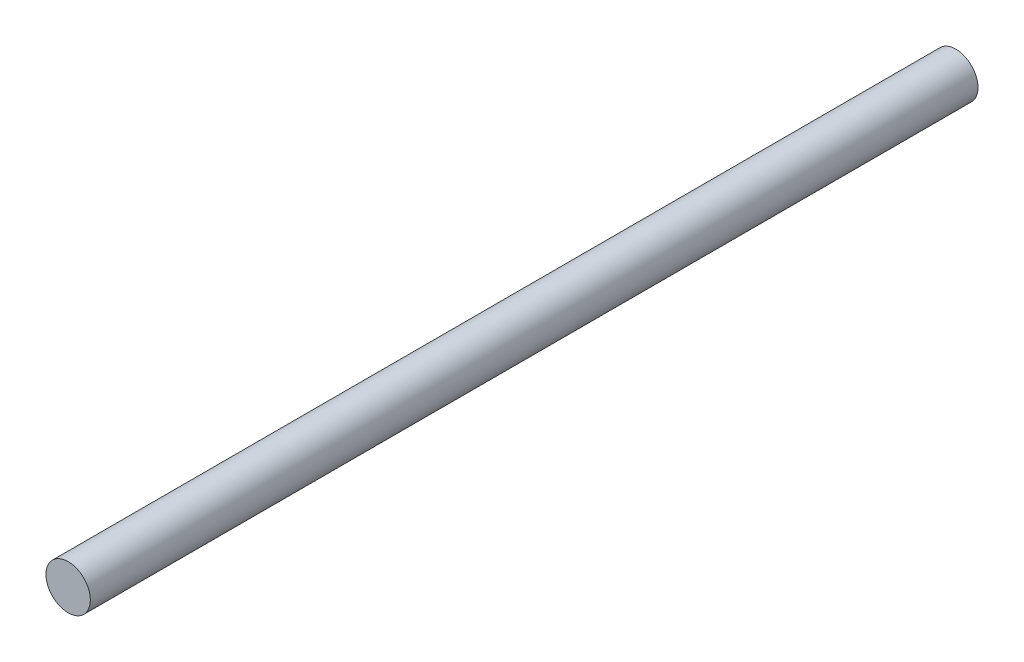
SolidWorks part; units mm, degrees
ref_plane "Front Plane" through (0, 0, 0) normal (0, 0, 1) x (1, 0, 0)
ref_plane "Top Plane" through (0, 0, 0) normal (0, 1, 0) x (1, 0, 0)
ref_plane "Right Plane" through (0, 0, 0) normal (1, 0, 0) x (0, 0, -1)
sketch "Sketch1" plane through (0, 0, 0) normal (0, 0, 1) x (1, 0, 0)
  circle A0 centre (0, 0) radius 3.175
  dimension "D1" = 6.35
extrude "Boss-Extrude1" add sketch "Sketch1" along normal blind 127
ref_axis "Axis1" through (0, 0, 127) along (0, 0, -1)
